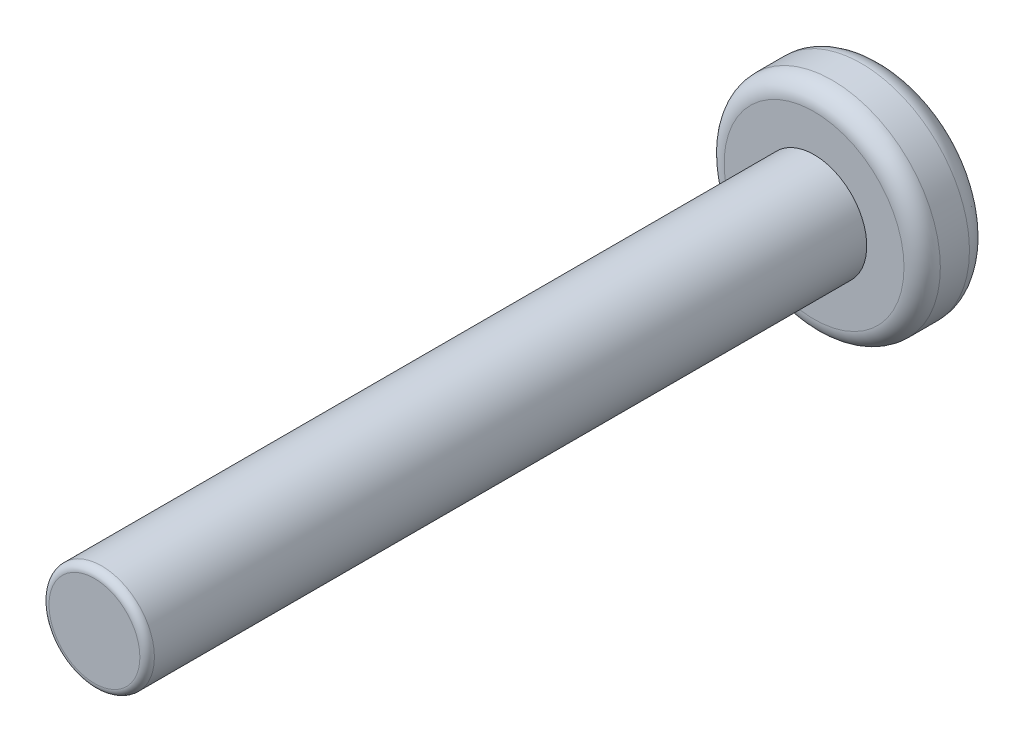
SolidWorks part; units mm, degrees
ref_plane "Plano frontal" through (0, 0, 0) normal (0, 0, 1) x (1, 0, 0)
ref_plane "Plano superior" through (0, 0, 0) normal (0, 1, 0) x (1, 0, 0)
ref_plane "Plano direito" through (0, 0, 0) normal (1, 0, 0) x (0, 0, -1)
sketch "Esboço1" plane through (0, 0, 0) normal (0, 0, 1) x (1, 0, 0)
  circle A0 centre (0, 0) radius 2.975
  dimension "D1" = 5.95
extrude "Ressalto-extrusão1" add sketch "Esboço1" along normal blind 2.3
fillet "Filete1" radius 2 1 edges at (2.975, 0, 0) second distance 1 first distance on face at (2.975, 0, 0)
fillet "Filete2" radius 0.5 1 edges at (2.975, 0, 2.3)
sketch "Esboço2" plane through (0, 0, 0) normal (0, 0, -1) x (-1, 0, 0)
  line L0 (2.1654, -0.385) -> (2.25, -0.4) construction
  line L5 (0.25, -2.25) -> (-0.25, -2.25)
  line L6 (0.4, -2.1) -> (0.4, -0.7)
  line L11 (0.25, 2.25) -> (-0.25, 2.25)
  line L12 (-0.4, -2.1) -> (-0.4, -0.7)
  line L13 (0.4, -2.25) -> (0.385, -2.1654) construction
  line L14 (0.4, 2.25) -> (0.385, 2.1654) construction
  line L15 (-2.1, 0.4) -> (-0.7, 0.4)
  line L20 (-2.25, 0.25) -> (-2.25, -0.25)
  line L21 (-2.1, -0.4) -> (-0.7, -0.4)
  line L22 (2.25, 0.25) -> (2.25, -0.25)
  line L23 (-2.25, 0.4) -> (-2.1654, 0.385) construction
  line L24 (-2.25, -0.4) -> (-2.1654, -0.385) construction
  line L25 (2.1654, 0.385) -> (2.25, 0.4) construction
  line L28 (-0.385, -2.1654) -> (-0.4, -2.25) construction
  line L29 (-0.385, 2.1654) -> (-0.4, 2.25) construction
  line L30 (0.7, 0.4) -> (2.1, 0.4)
  line L31 (-0.4, 0.7) -> (-0.4, 2.1)
  line L32 (0.4, 0.7) -> (0.4, 2.1)
  line L33 (0.7, -0.4) -> (2.1, -0.4)
  arc A12 (-0.25, 2.25) -> (-0.4, 2.1) centre (-0.25, 2.1) ccw
  arc A13 (0.4, 2.1) -> (0.25, 2.25) centre (0.25, 2.1) ccw
  arc A14 (2.1, 0.4) -> (2.25, 0.25) centre (2.1, 0.25) cw
  arc A15 (2.1, -0.4) -> (2.25, -0.25) centre (2.1, -0.25) ccw
  arc A16 (0.25, -2.25) -> (0.4, -2.1) centre (0.25, -2.1) ccw
  arc A17 (-0.25, -2.25) -> (-0.4, -2.1) centre (-0.25, -2.1) cw
  arc A18 (-2.25, -0.25) -> (-2.1, -0.4) centre (-2.1, -0.25) ccw
  arc A19 (-2.1, 0.4) -> (-2.25, 0.25) centre (-2.1, 0.25) ccw
  arc A20 (-0.7, 0.4) -> (-0.4, 0.7) centre (-0.7, 0.7) ccw
  arc A21 (0.7, 0.4) -> (0.4, 0.7) centre (0.7, 0.7) cw
  arc A22 (0.4, -0.7) -> (0.7, -0.4) centre (0.7, -0.7) cw
  arc A23 (-0.4, -0.7) -> (-0.7, -0.4) centre (-0.7, -0.7) ccw
  point P0 (0, 0)
  point P6 (0, 0)
  point P50 (-0.4, 0.4)
  point P53 (0.4, 0.4)
  point P56 (0.4, -0.4)
  dimension "D5" = 0.15
  dimension "D6" = 0.3
  dimension "D1" = 0.8
  dimension "D2" = 0.8
  dimension "D3" = 4.5
  dimension "D4" = 4.5
extrude "Corte-extrusão1" cut sketch "Esboço2" against normal blind 1.3
sketch "Esboço3" plane through (0, 0, 2.3) normal (0, 0, 1) x (1, 0, 0)
  circle A0 centre (0, 0) radius 1.45
  dimension "D1" = 2.9
extrude "Ressalto-extrusão2" add sketch "Esboço3" along normal blind 19.8
fillet "Filete3" radius 0.2 1 edges at (1.45, 0, 22.1)
